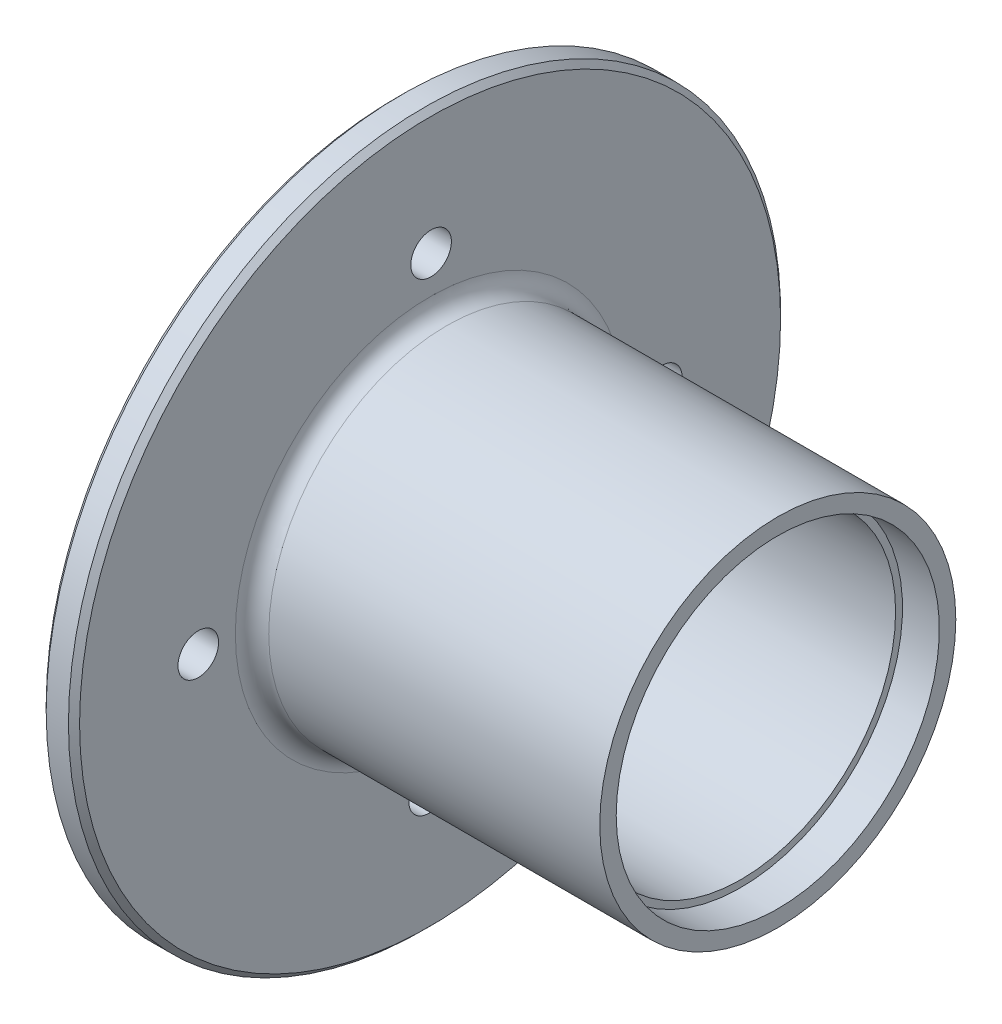
SolidWorks part; units mm, degrees
ref_plane "Front" through (0, 0, 0) normal (0, 0, 1) x (1, 0, 0)
ref_plane "Top" through (0, 0, 0) normal (0, 1, 0) x (1, 0, 0)
ref_plane "Right" through (0, 0, 0) normal (1, 0, 0) x (0, 0, -1)
other "Configuration Table"
sketch "Sketch1" plane through (0, 0, 0) normal (0, 0, 1) x (1, 0, 0)
  line L6 (4.7625, 12.547) -> (4.7625, 17.1434)
  line L7 (4.7625, 17.1434) -> (20.2028, 17.1434)
  line L8 (20.2028, 17.1434) -> (20.2028, 22.068)
  line L9 (20.2028, 22.068) -> (49.1124, 22.068)
  line L10 (49.1124, 22.068) -> (49.1124, 23.0529)
  line L12 (54.3687, 23.0529) -> (54.3687, 25.4)
  line L13 (54.3687, 25.4) -> (7.1438, 25.4)
  line L14 (4.7625, 27.7812) -> (4.7625, 50.0062)
  line L15 (3.9687, 50.8) -> (0.7938, 50.8)
  line L16 (0, 50.0062) -> (0, 17.1434)
  line L17 (0, 17.1434) -> (4.7625, 12.547)
  line L18 (49.1124, 23.0529) -> (54.3687, 23.0529)
  line L19 (4.7625, 50.0062) -> (3.9687, 50.8)
  line L20 (0.7938, 50.8) -> (0, 50.0062)
  line L21 (207.4989, 0) -> (272.5603, 0) construction
  arc A3 (4.7625, 27.7812) -> (7.1438, 25.4) centre (7.1438, 27.7812) ccw
  dimension "D2" = 2.3813
  dimension "D1" = 47.2249
  dimension "D3" = 0.7938
  dimension "D4" = 3.9687
  dimension "D5" = 4.7625
  dimension "D6" = 20.2028
  dimension "D7" = 49.1124
  dimension "D8" = 12.547
  dimension "D9" = 17.1434
  dimension "D10" = 22.068
  dimension "D11" = 23.0529
  dimension "D12" = 25.4
  dimension "D13" = 50.0062
  dimension "D14" = 50.8
revolve "Revolve1" add sketch "Sketch1" angle 360 about L21
hole_wizard "#12 Clearance Hole1" positions "3DSketch1" profile "Sketch2" hole size "#12" standard "Ansi Inch" end condition through all
sketch3d "3DSketch1"
  circle A0 centre (0, 0, 0) radius 50.0062 construction
  point P0 (0, 33.069, -0.147)
  point P3 (-50.0062, 0, 0)
  dimension "D1" = 33.0693
sketch "Sketch2" plane through (0, 33.069, -0.147) normal (0, 1, 0) x (0, 0, 1)
  line L0 (0, 0) -> (0, 54.3687)
  line L1 (0, 54.3687) -> (2.8956, 54.3687)
  line L2 (2.8956, 54.3687) -> (2.8956, 0)
  line L5 (2.8956, 0) -> (0, 0)
  line L11 (0, -6.35) -> (0, 107.95) construction
  dimension "Thru Hole Dia." = 5.7912
  dimension "Thru Hole Depth" = 54.3687
ref_axis "Axis1" through (54.3687, 0, 0) along (-1, 0, 0)
pattern_circular "CirPattern1" count 4 over 360 about axis through (54.3687, 0, 0) along (-1, 0, 0) of "#12 Clearance Hole1"
